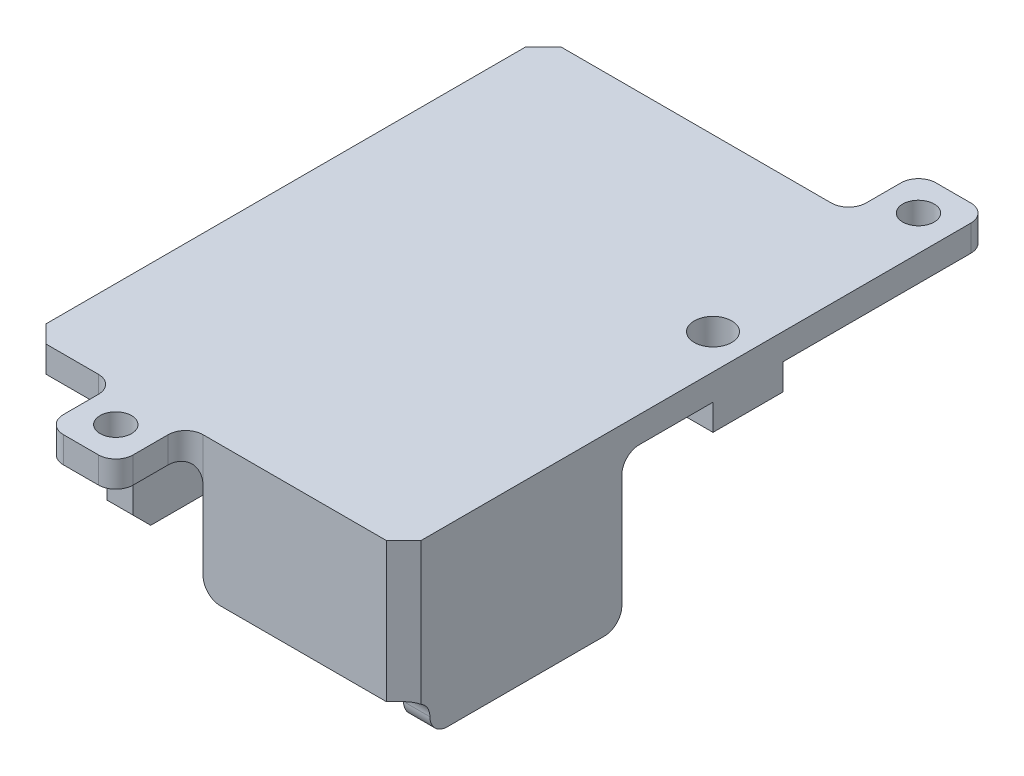
SolidWorks part; units mm, degrees
ref_plane "Płaszczyzna przednia" through (0, 0, 0) normal (0, 0, 1) x (1, 0, 0)
ref_plane "Płaszczyzna górna" through (0, 0, 0) normal (0, 1, 0) x (1, 0, 0)
ref_plane "Płaszczyzna prawa" through (0, 0, 0) normal (1, 0, 0) x (0, 0, -1)
sketch "Sketch1" plane through (0, 0, 0) normal (0, 1, 0) x (1, 0, 0)
  line L1 (0, 0) -> (43, 0)
  line L2 (0, 0) -> (0, 59)
  line L3 (0, 59) -> (43, 59)
  line L4 (43, 0) -> (43, 59)
  dimension "D1" = 59
  dimension "D2" = 43
extrude "Boss-Extrude1" add sketch "Sketch1" along normal blind 3
chamfer "Chamfer1" distance 2 angle 45 2 edges at (0, 1.5, 0) (0, 1.5, -59)
sketch "Sketch2" plane through (0, 0, 0) normal (-1, 0, 0) x (0, 0, 1)
  line L0 (-57, 3) -> (-2, 3) construction
  line L1 (-50, 3) -> (-31, 3)
  line L2 (-50, 3) -> (-50, -3)
  line L3 (-50, -3) -> (-31, -3)
  line L4 (-31, 3) -> (-31, -3)
  line L5 (-59, 0) -> (-59, 3) construction
  line L6 (0, 3) -> (0, 0) construction
  line L7 (-22.5, 3) -> (-9, 3)
  line L8 (-22.5, 3) -> (-22.5, -20)
  line L9 (-22.5, -20) -> (-9, -20)
  line L10 (-9, 3) -> (-9, -20)
  dimension "D1" = 9
  dimension "D2" = 19
  dimension "D3" = 6
  dimension "D4" = 9
  dimension "D5" = 13.5
  dimension "D6" = 23
extrude "Boss-Extrude2" add sketch "Sketch2" against normal blind 3
chamfer "Chamfer2" distance 2 angle 45 4 edges at (1.5, -20, -9) (1.5, -20, -22.5) (1.5, -3, -31) (1.5, -3, -50)
fillet "Fillet1" radius 2 4 edges at (1.5, 0, -50) (1.5, 0, -31) (1.5, 0, -9) (1.5, 0, -22.5)
sketch "Sketch3" plane through (0, 3, 0) normal (0, 1, 0) x (1, 0, 0)
  line L0 (43, 59) -> (2, 59) construction
  line L1 (35, 67) -> (43, 67)
  line L2 (35, 67) -> (35, 59)
  line L3 (35, 59) -> (43, 59)
  line L4 (43, 67) -> (43, 59)
  line L5 (35, 67) -> (43, 59) construction
  line L6 (35, 59) -> (43, 67) construction
  line L7 (43, 65) -> (43, 57) construction
  line L8 (35, 65) -> (35, 61) construction
  line L9 (2, 0) -> (43, 0) construction
  line L10 (10, -8) -> (18, -8)
  line L11 (10, -8) -> (10, 0)
  line L12 (10, 0) -> (18, 0)
  line L13 (18, -8) -> (18, 0)
  line L14 (10, -8) -> (18, 0) construction
  line L15 (10, 0) -> (18, -8) construction
  line L16 (18, 2) -> (18, -6) construction
  line L17 (10, -2) -> (10, -6) construction
  circle A0 centre (39, 63) radius 1.8
  circle A1 centre (14, -4) radius 1.8
  point P0 (39, 63)
  point P13 (14, -4)
  dimension "D1" = 3.6
  dimension "D2" = 3.6
extrude "Boss-Extrude3" add sketch "Sketch3" against normal up to surface (3 mm away) up to face at (7.2857, 0, -28.7143)
fillet "Fillet2" radius 2 7 edges at (18, 1.5, 0) (18, 1.5, 8) (10, 1.5, 0) (10, 1.5, 8) (35, 1.5, -59) (35, 1.5, -67) (43, 1.5, -67)
sketch "Sketch4" plane through (0, 0, 0) normal (0, 0, 1) x (1, 0, 0)
  line L0 (43, 3) -> (43, 0) construction
  line L1 (20, 3) -> (43, 3)
  line L2 (20, 3) -> (20, -17)
  line L3 (20, -17) -> (43, -17)
  line L4 (43, 3) -> (43, -17)
  dimension "D1" = 20
extrude "Boss-Extrude4" add sketch "Sketch4" against normal blind 3
sketch "Sketch5" plane through (43, 0, 0) normal (1, 0, 0) x (0, 0, -1)
  line L0 (3, -17) -> (0, -17) construction
  line L1 (0, 3) -> (25, 3)
  line L2 (0, 3) -> (0, -17)
  line L3 (0, -17) -> (25, -17)
  line L4 (25, 3) -> (25, -17)
  dimension "D1" = 25
extrude "Boss-Extrude5" add sketch "Sketch5" against normal blind 3
chamfer "Chamfer3" distance 2 angle 45 2 edges at (40, -8.5, -3) (43, -7, 0)
fillet "Fillet4" radius 2 4 edges at (20, 0, -1.5) (41.5, 0, -25) (41.5, -17, -25) (20, -17, -1.5)
sketch "Sketch6" plane through (0, 3, 0) normal (0, 1, 0) x (1, 0, 0)
  line L8 (35, 35.45) -> (43, 35.45)
  line L9 (35, 35.45) -> (35, 43.45)
  line L10 (35, 43.45) -> (43, 43.45)
  line L11 (43, 35.45) -> (43, 43.45)
  line L12 (35, 35.45) -> (43, 43.45) construction
  line L13 (35, 43.45) -> (43, 35.45) construction
  line L14 (43, 2) -> (43, 65) construction
  line L15 (33, 59) -> (2, 59) construction
  circle A0 centre (39, 39.45) radius 2.15
  point P0 (39, 39.45)
  dimension "D2" = 4.3
  dimension "D1" = 8
  dimension "D3" = 15.55
extrude "Boss-Extrude6" add sketch "Sketch6" against normal blind 6
fillet "Fillet5" radius 2 2 edges at (35, -1.5, -43.45) (35, -1.5, -35.45)
hole_wizard "Ø4.3 (4.3) Diameter Hole1" positions "Sketch7" profile "Sketch8" hole size "Ø4.3" standard "DIN" end condition through all
sketch "Sketch7" plane through (0, -3, 0) normal (0, -1, 0) x (-1, 0, 0)
  point P0 (-39, 39.45)
sketch "Sketch8" plane through (39, -3, -39.45) normal (1, 0, 0) x (0, 0, -1)
  line L0 (0, 0) -> (0, 6)
  line L1 (0, 6) -> (2.15, 6)
  line L2 (2.15, 6) -> (2.15, 0)
  line L5 (2.15, 0) -> (0, 0)
  line L11 (0, -6.35) -> (0, 107.95) construction
  dimension "Thru Hole Dia." = 4.3
  dimension "Thru Hole Depth" = 6
sketch "Sketch9" plane through (0, 0, 0) normal (0, 0, 1) x (1, 0, 0)
  line L0 (20, -2) -> (20, -15) construction
  line L1 (43, -17) -> (20, -17)
  line L2 (43, -17) -> (43, -13)
  line L3 (43, -13) -> (20, -13)
  line L4 (20, -17) -> (20, -13)
  dimension "D1" = 4
extrude "Cut-Extrude1" cut sketch "Sketch9" against normal up to surface (3 mm away) up to face at (26, -8.5, -3)
chamfer "Chamfer4" distance 2.8 angle 45 1 edges at (38, -15, -3) first distance on face at (38.8, -9.4, -3.8)
fillet "Fillet6" radius 2 3 edges at (41.4899, -17, -3) (41.4899, -13, -3) (20, -13, -1.5)
